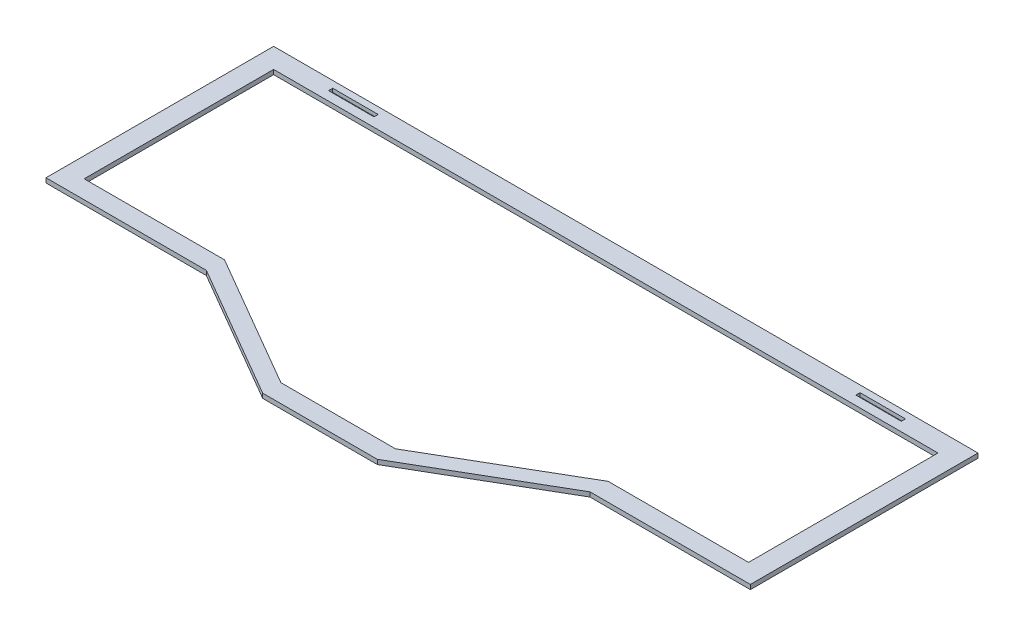
SolidWorks part; units mm, degrees
ref_plane "Front Plane" through (0, 0, 0) normal (0, 0, 1) x (1, 0, 0)
ref_plane "Top Plane" through (0, 0, 0) normal (0, 1, 0) x (1, 0, 0)
ref_plane "Right Plane" through (0, 0, 0) normal (1, 0, 0) x (0, 0, -1)
sketch "Sketch1" plane through (0, 0, 0) normal (0, 1, 0) x (1, 0, 0)
  line L1 (-193.7, 84.7) -> (193.7, 84.7)
  line L2 (-193.7, 84.7) -> (-193.7, -84.7)
  line L3 (-193.7, -84.7) -> (193.7, -84.7)
  line L4 (193.7, 84.7) -> (193.7, -84.7)
  line L5 (-193.7, 84.7) -> (193.7, -84.7) construction
  line L6 (-193.7, -84.7) -> (193.7, 84.7) construction
  point P0 (0, 0)
  dimension "D1" = 387.4
  dimension "D2" = 169.4
extrude "Boss-Extrude1" add sketch "Sketch1" along normal blind 2.5
sketch "Sketch3" plane through (0, 2.5, 0) normal (0, 1, 0) x (1, 0, 0)
  line L0 (193.7, 84.7) -> (157.5, 84.7) construction
  line L1 (193.7, 84.7) -> (-193.7, 84.7) construction
  line L2 (157.5, 81) -> (157.5, 78.7)
  line L4 (157.5, 78.7) -> (132.5, 78.7)
  line L6 (132.5, 78.7) -> (132.5, 81)
  line L7 (132.5, 81) -> (157.5, 81)
  line L8 (157.5, 84.7) -> (157.5, 78.7) construction
  line L9 (-193.7, 84.7) -> (-157.5, 84.7) construction
  line L10 (-157.5, 81) -> (-157.5, 78.7)
  line L11 (-157.5, 78.7) -> (-132.5, 78.7)
  line L12 (-132.5, 78.7) -> (-132.5, 81)
  line L13 (-132.5, 81) -> (-157.5, 81)
  line L14 (-157.5, 84.7) -> (-157.5, 78.7) construction
  point P7 (0, 0)
  dimension "D1" = 36.2
  dimension "D2" = 2.3
  dimension "D3" = 25
  dimension "D4" = 36.2
  dimension "D5" = 2.3
  dimension "D6" = 25
  dimension "D7" = 6
  dimension "D8" = 6
extrude "Cut-Extrude2" cut sketch "Sketch3" against normal blind 2
sketch "Sketch4" plane through (0, 0, 0) normal (0, -1, 0) x (1, 0, 0)
  line L0 (31.5, 73.5) -> (105.5, 30.5)
  line L1 (105.5, 30.5) -> (182.7, 30.5)
  line L2 (182.7, 30.5) -> (182.7, -73.7)
  line L3 (182.7, -73.7) -> (-182.7, -73.7)
  line L4 (-182.7, -73.7) -> (-182.7, 30.5)
  line L5 (-182.7, 30.5) -> (-105.5, 30.5)
  line L6 (-105.5, 30.5) -> (-31.5, 73.5)
  line L7 (-31.5, 73.5) -> (31.5, 73.5)
  line L8 (-144.1, 30.5) -> (-144.1, 84.7) construction
  line L9 (-193.7, 84.7) -> (193.7, 84.7) construction
  line L10 (0, 73.5) -> (0, 84.7) construction
  line L11 (144.1, 30.5) -> (144.1, 84.7) construction
  line L12 (0, -73.7) -> (0, -84.7) construction
  line L13 (193.7, -84.7) -> (-193.7, -84.7) construction
  line L14 (-182.7, -21.6) -> (-193.7, -21.6) construction
  line L15 (-193.7, -84.7) -> (-193.7, 84.7) construction
  line L16 (182.7, -21.6) -> (193.7, -21.6) construction
  line L17 (193.7, 84.7) -> (193.7, -84.7) construction
  line L18 (-105.5, 30.5) -> (-105.5, 35.5) construction
  line L19 (105.5, 30.5) -> (105.5, 35.5) construction
  dimension "D1" = 54.2
  dimension "D2" = 11.2
  dimension "D3" = 11
  dimension "D4" = 11
extrude "Cut-Extrude3" cut sketch "Sketch4" against normal blind 10
sketch "Sketch7" plane through (0, 0, 0) normal (0, -1, 0) x (1, 0, 0)
  line L0 (193.7, 40.5) -> (105.5, 40.5)
  line L1 (193.7, 84.7) -> (193.7, -84.7) construction
  line L2 (105.5, 40.5) -> (31.5, 83.5)
  line L3 (31.5, 83.5) -> (-31.5, 83.5)
  line L4 (-31.5, 83.5) -> (-105.5, 40.5)
  line L5 (-105.5, 40.5) -> (-193.7, 40.5)
  line L6 (-193.7, -84.7) -> (-193.7, 84.7) construction
  line L7 (-144.1, 30.5) -> (-144.1, 40.5) construction
  line L8 (-105.5, 30.5) -> (-182.7, 30.5) construction
  line L9 (-105.5, 30.5) -> (-105.5, 40.5) construction
  line L10 (105.5, 30.5) -> (105.5, 40.5) construction
  line L11 (144.1, 30.5) -> (144.1, 40.5) construction
  line L12 (182.7, 30.5) -> (105.5, 30.5) construction
  line L13 (0, 73.5) -> (0, 83.5) construction
  line L14 (31.5, 73.5) -> (-31.5, 73.5) construction
  line L15 (-31.5, 73.5) -> (-31.5, 83.5) construction
  line L16 (31.5, 73.5) -> (31.5, 83.5) construction
  line L17 (-193.7, 40.5) -> (-193.7, 84.7)
  line L18 (-193.7, 84.7) -> (193.7, 84.7)
  line L19 (193.7, 84.7) -> (193.7, 40.5)
  dimension "D1" = 10
  dimension "D2" = 10
  dimension "D3" = 10
extrude "Cut-Extrude4" cut sketch "Sketch7" against normal through all
equation "\"full_width\"=375"
equation "\"D1@Sketch1\"=\"full_width\"+(\"added_width\"*2)+(\"margin1\"*2)"
equation "\"added_width\"=6"
equation "\"full_height\"= 157"
equation "\"D2@Sketch1\"=\"full_height\"+(\"added_height\"*2)+(\"margin1\"*2)"
equation "\"added_height\"=6"
equation "\"D1@Sketch3\"=30.00mm+\"added_width\"+\"margin1\""
equation "\"tab_depth\"=2.5"
equation "\"D2@Sketch3\"=\"tab_depth\"-\"margin1\""
equation "\"tab_width\"=25"
equation "\"D3@Sketch3\"=\"tab_width\""
equation "\"tab_height\"=2"
equation "\"D1@Cut-Extrude2\"=\"tab_height\""
equation "\"D4@Sketch3\"=30mm+\"added_width\"+\"margin1\""
equation "\"D5@Sketch3\"=\"tab_depth\"-\"margin1\""
equation "\"D6@Sketch3\"=\"tab_width\""
equation "\"margin1\"= 0.2"
equation "\"angle_dist\"=32.037"
equation "\"chin_dist\"=6.2"
equation "\"D2@Sketch4\"=\"chin_dist\"+5"
equation "\"flat_dist\"=49.2"
equation "\"D1@Sketch4\"=\"flat_dist\"+5"
equation "\"D3@Sketch4\"=\"added_height\"+5"
equation "\"D4@Sketch4\"=\"added_width\"+5"
equation "\"D7@Sketch3\"=\"added_height\""
equation "\"D8@Sketch3\"=\"added_height\""
